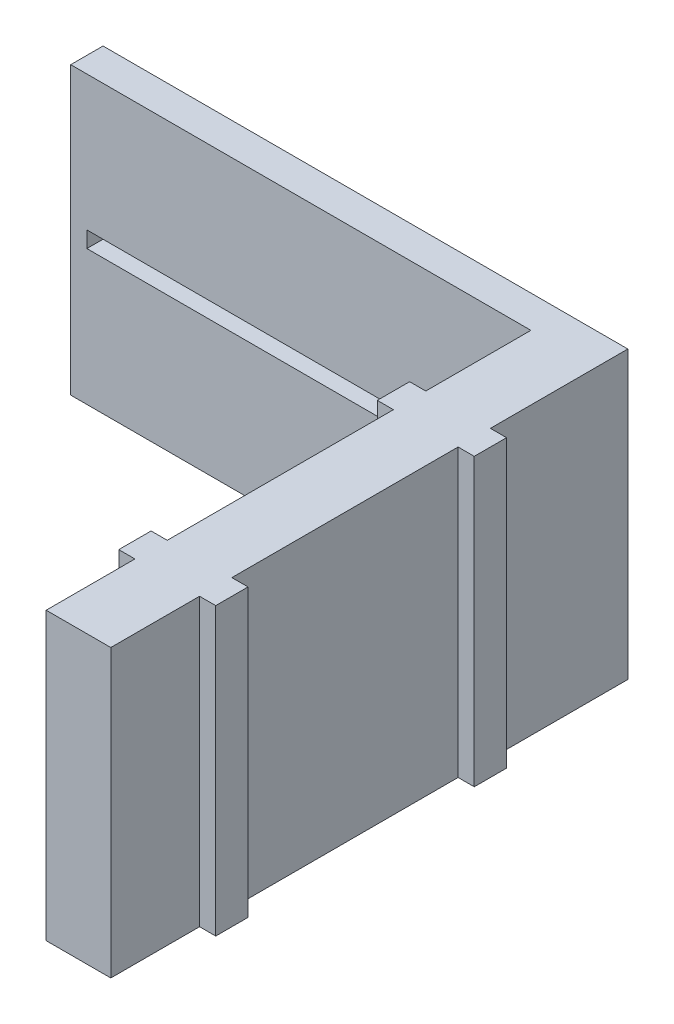
SolidWorks part; units mm, degrees
ref_plane "Front Plane" through (0, 0, 0) normal (0, 0, 1) x (1, 0, 0)
ref_plane "Top Plane" through (0, 0, 0) normal (0, 1, 0) x (1, 0, 0)
ref_plane "Right Plane" through (0, 0, 0) normal (1, 0, 0) x (0, 0, -1)
sketch "Sketch2" plane through (0, 0, 0) normal (1, 0, 0) x (0, 0, -1)
  line L1 (-80, 44.2846) -> (80, 44.2846)
  line L2 (-80, 44.2846) -> (-80, -44.2846)
  line L3 (-80, -44.2846) -> (80, -44.2846)
  line L4 (80, 44.2846) -> (80, -44.2846)
  line L5 (-80, 44.2846) -> (80, -44.2846) construction
  line L6 (-80, -44.2846) -> (80, 44.2846) construction
  point P0 (0, 0)
  dimension "D1" = 160
extrude "Boss-Extrude1" add sketch "Sketch2" along normal blind 10
sketch "Sketch3" plane through (0, 0, 0) normal (-1, 0, 0) x (0, 0, 1)
  line L0 (-70, 44.2846) -> (-70, -44.2846)
  line L1 (-80, 44.2846) -> (80, 44.2846) construction
  line L2 (80, -44.2846) -> (-80, -44.2846) construction
  line L3 (-70, -44.2846) -> (-80, -44.2846)
  line L4 (-80, -44.2846) -> (-80, 44.2846)
  line L5 (-80, 44.2846) -> (-70, 44.2846)
  dimension "D1" = 10
extrude "Boss-Extrude2" add sketch "Sketch3" along normal blind 152.4
sketch "Sketch4" plane through (-152.4, 0, 0) normal (-1, 0, 0) x (0, 0, 1)
  line L0 (-70, 44.2846) -> (-80, -44.2846) construction
  line L1 (-70, 44.2846) -> (-80, 44.2846) construction
  line L2 (-70, -44.2846) -> (-70, 44.2846) construction
  line L3 (-70, -44.2846) -> (-70, 44.2846) construction
  line L4 (-80, 44.2846) -> (-70, -44.2846) construction
  line L5 (-80, -2.5) -> (-70, -2.5)
  line L6 (-80, -2.5) -> (-80, 2.5)
  line L7 (-80, 2.5) -> (-70, 2.5)
  line L8 (-70, -2.5) -> (-70, 2.5)
  line L9 (-80, -2.5) -> (-70, 2.5) construction
  line L10 (-80, 2.5) -> (-70, -2.5) construction
  point P7 (-75, 0)
  dimension "D1" = 5
extrude "Cut-Extrude6" cut sketch "Sketch4" against normal blind 152.4
extrude "Boss-Extrude3" add sketch "Sketch4<2>" against normal blind 5 contours L5 L8 L7 L6
sketch "Sketch4<2>" plane through (-152.4, 0, 0) normal (-1, 0, 0) x (0, 0, 1) same geometry as "Sketch4"
sketch "Sketch6" plane through (10, 0, 0) normal (1, 0, 0) x (0, 0, -1)
  line L0 (80, 44.2846) -> (80, -44.2846) construction
  line L1 (80, -44.2846) -> (70, -44.2846) construction
  line L2 (-80, -44.2846) -> (80, -44.2846) construction
  line L3 (70, -44.2846) -> (70, 44.2846) construction
  line L4 (80, 44.2846) -> (-80, 44.2846) construction
  line L5 (70, 44.2846) -> (80, 44.2846) construction
  line L6 (70, 44.2846) -> (37.47, 44.2846)
  line L7 (37.47, 44.2846) -> (37.47, -44.2846)
  line L8 (37.47, -44.2846) -> (27.47, -44.2846)
  line L9 (27.47, -44.2846) -> (27.47, 44.2846)
  line L10 (27.47, 44.2846) -> (37.47, 44.2846)
  line L12 (-42.53, 44.2846) -> (-52.53, 44.2846)
  line L13 (-42.53, -44.2846) -> (-42.53, 44.2846)
  line L14 (-52.53, -44.2846) -> (-42.53, -44.2846)
  line L15 (-52.53, 44.2846) -> (-52.53, -44.2846)
  line M5 (80, 44.2846) -> (-80, 44.2846)
  line M7 (-80, -44.2846) -> (80, -44.2846)
  dimension "D1" = 10
  dimension "D2" = 32.53
  dimension "D3" = 10
  dimension "D4" = 70
  dimension "D5" = 10
extrude "Boss-Extrude4" add sketch "Sketch6" along normal blind 5 contours L9 L7 M7 M5 | L15 L14 L13 L12 region at (10, 0, -32.47)
mirror "Mirror2" about plane through (0, 0, 0) normal (1, 0, 0) of "Boss-Extrude4", "Boss-Extrude1"
